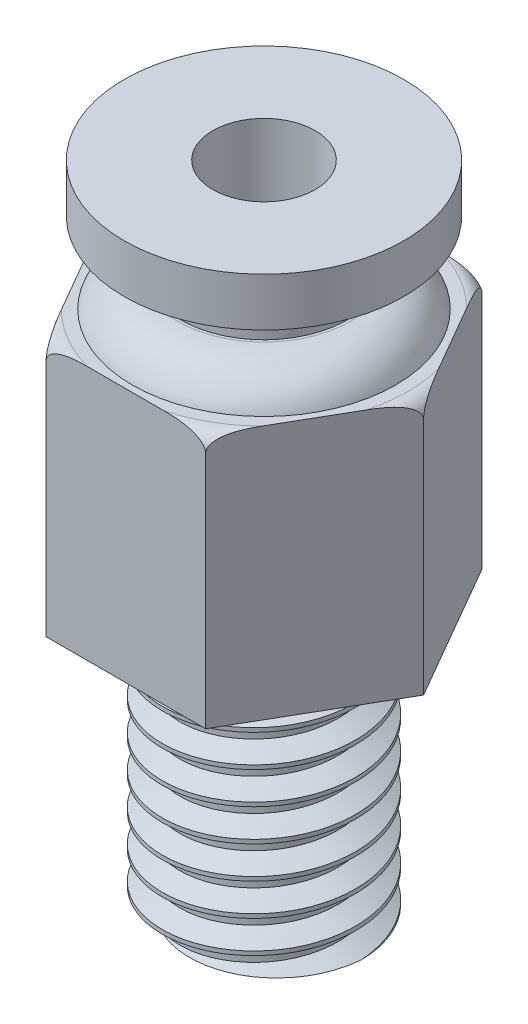
SolidWorks part; units mm, degrees
material "Acero inoxidable fundido"
ref_plane "Alzado" through (0, 0, 0) normal (0, 0, 1) x (1, 0, 0)
ref_plane "Planta" through (0, 0, 0) normal (0, 1, 0) x (1, 0, 0)
ref_plane "Vista lateral" through (0, 0, 0) normal (1, 0, 0) x (0, 0, -1)
sketch "Croquis1" plane through (0, 0, 0) normal (0, 0, 1) x (1, 0, 0)
  line L0 (-1.5875, 0) -> (-3, 0)
  line L1 (-3, 0) -> (-3, 8.1)
  line L2 (-3, 8.1) -> (-4.95, 8.1)
  line L3 (-4.95, 8.1) -> (-4.95, 16)
  line L4 (-4.95, 16) -> (-4.0875, 16)
  line L5 (-4.0875, 16) -> (-4.0875, 17)
  line L6 (-4.0875, 17) -> (-1.5875, 17)
  line L7 (-1.5875, 17) -> (-1.5875, 0)
  line L8 (-4.3375, 20) -> (-1.5875, 20)
  line L9 (-2.5875, 18.5) -> (-4.3375, 18.5)
  line L10 (-4.3375, 18.5) -> (-4.3375, 20)
  line L11 (-1.5875, 20) -> (-1.5875, 17)
  line L12 (-2.5875, 18.5) -> (-2.5875, 17)
  line L13 (0, 0) -> (0, 8.7797) construction
  dimension "D1" = 1.5875
  dimension "D2" = 3
  dimension "D3" = 4.95
  dimension "D4" = 8.1
  dimension "D5" = 20
  dimension "D6" = 1.5
  dimension "D7" = 1.5
  dimension "D8" = 1
  dimension "D9" = 2.5
  dimension "D10" = 1
  dimension "D11" = 2.75
  dimension "D12" = 7.9
revolve "Revolución1" add sketch "Croquis1" angle 360 about L13 region at (-2.9667, 10.0649, 0)
fillet "Redondeo1" radius 1.5 1 edges at (0, 17, -4.0875)
fillet "Redondeo2" radius 0.5 1 edges at (0, 16, -4.95)
thread "Rosca1" pitch 1 method cut profile "Perfil de rosca1" start angle 0, offset 1, length 10, pitch 1, diameter 6
ref_plane "Plano1" through (3, -1, 0) normal (0, 0, 1) x (1, 0, 0)
sketch "Perfil de rosca1" plane through (3, -1, 0) normal (0, 0, 1) x (1, 0, 0)
  line L0 (0, 0) -> (0, 1) construction
  line L11 (0, 0) -> (0, 0.875)
  line L12 (0, 0.875) -> (-0.5413, 0.5625)
  line L13 (-0.5413, 0.5625) -> (-0.5413, 0.3125)
  line L15 (-0.5413, 0.3125) -> (0, 0)
  line L17 (-0.5413, 0.4375) -> (0, 0.4375) construction
  point P2 (0, 0)
  dimension "Pitch" = 1
  dimension "Profile_Angle" = 60
  dimension "Profile_Land" = 0.25
  dimension "Profile_Height" = 0.5413
sketch "Croquis5" plane through (0, 0, 0) normal (0, 0, 1) x (1, 0, 0)
  line L0 (-1.5875, 20) -> (-1.5875, 17) construction
  line L1 (-4.3375, 20) -> (-1.5875, 20) construction
  line L2 (-4.3375, 18.5) -> (-4.3375, 20) construction
  line L3 (-2.5875, 18.5) -> (-4.3375, 18.5) construction
  line L4 (-2.5875, 18.5) -> (-2.5875, 17) construction
  line L5 (-4.0875, 17) -> (-1.5875, 17) construction
  line L6 (-4.0875, 16) -> (-4.0875, 17) construction
  line L7 (-4.95, 16) -> (-4.0875, 16) construction
  line L8 (-4.95, 8.1) -> (-4.95, 16) construction
  line L9 (-3, 8.1) -> (-4.95, 8.1) construction
  line L10 (-3, 0) -> (-3, 8.1) construction
  line L11 (-1.5875, 0) -> (-3, 0) construction
  line L12 (-1.5875, 17) -> (-1.5875, 0) construction
  line L13 (-1.5875, 20) -> (-1.5875, 17)
  line L14 (-4.3375, 20) -> (-1.5875, 20)
  line L15 (-4.3375, 18.5) -> (-4.3375, 20)
  line L16 (-2.5875, 18.5) -> (-4.3375, 18.5)
  line L17 (-2.5875, 18.5) -> (-2.5875, 17)
  line L18 (-4.0875, 17) -> (-1.5875, 17)
  line L19 (-4.0875, 16) -> (-4.0875, 17)
  line L20 (-4.95, 16) -> (-4.0875, 16)
  line L21 (-4.95, 8.1) -> (-4.95, 16)
  line L22 (-3, 8.1) -> (-4.95, 8.1)
  line L23 (-3, 0) -> (-3, 8.1)
  line L24 (-1.5875, 0) -> (-3, 0)
  line L25 (-1.5875, 17) -> (-1.5875, 0)
  line L26 (0, 0) -> (0, 5.0625) construction
  spline S0 degree 2 poles (-0.9409, 0) (-0.4891, 0.0325) (0, 0.0625) (1.0184, 0.125) (1.7386, 0.1875) (2.4587, 0.25) (2.4587, 0.3125) (2.4587, 0.375) (1.7386, 0.4375) (1.0184, 0.5) (0, 0.5625) (-1.0184, 0.625) (-1.7386, 0.6875) (-2.4587, 0.75) (-2.4587, 0.8125) (-2.4587, 0.875) (-1.7386, 0.9375) (-1.0184, 1) (0, 1.0625) (1.0184, 1.125) (1.7386, 1.1875) (2.4587, 1.25) (2.4587, 1.3125) (2.4587, 1.375) (1.7386, 1.4375) (1.0184, 1.5) (0, 1.5625) (-1.0184, 1.625) (-1.7386, 1.6875) (-2.4587, 1.75) (-2.4587, 1.8125) (-2.4587, 1.875) (-1.7386, 1.9375) (-1.0184, 2) (0, 2.0625) (1.0184, 2.125) (1.7386, 2.1875) (2.4587, 2.25) (2.4587, 2.3125) (2.4587, 2.375) (1.7386, 2.4375) (1.0184, 2.5) (0, 2.5625) (-1.0184, 2.625) (-1.7386, 2.6875) (-2.4587, 2.75) (-2.4587, 2.8125) (-2.4587, 2.875) (-1.7386, 2.9375) (-1.0184, 3) (0, 3.0625) (1.0184, 3.125) (1.7386, 3.1875) (2.4587, 3.25) (2.4587, 3.3125) (2.4587, 3.375) (1.7386, 3.4375) (1.0184, 3.5) (0, 3.5625) (-1.0184, 3.625) (-1.7386, 3.6875) (-2.4587, 3.75) (-2.4587, 3.8125) (-2.4587, 3.875) (-1.7386, 3.9375) (-1.0184, 4) (0, 4.0625) (1.0184, 4.125) (1.7386, 4.1875) (2.4587, 4.25) (2.4587, 4.3125) (2.4587, 4.375) (1.7386, 4.4375) (1.0184, 4.5) (0, 4.5625) (-1.0184, 4.625) (-1.7386, 4.6875) (-2.4587, 4.75) (-2.4587, 4.8125) (-2.4587, 4.875) (-1.7386, 4.9375) (-1.0184, 5) (0, 5.0625) (1.0184, 5.125) (1.7386, 5.1875) (2.4587, 5.25) (2.4587, 5.3125) (2.4587, 5.375) (1.7386, 5.4375) (1.0184, 5.5) (0, 5.5625) (-1.0184, 5.625) (-1.7386, 5.6875) (-2.4587, 5.75) (-2.4587, 5.8125) (-2.4587, 5.875) (-1.7386, 5.9375) (-1.0184, 6) (0, 6.0625) (1.0184, 6.125) (1.7386, 6.1875) (2.4587, 6.25) (2.4587, 6.3125) (2.4587, 6.375) (1.7386, 6.4375) (1.0184, 6.5) (0, 6.5625) (-1.0184, 6.625) (-1.7386, 6.6875) (-2.4587, 6.75) (-2.4587, 6.8125) (-2.4587, 6.875) (-1.7386, 6.9375) (-1.0184, 7) (0, 7.0625) (1.0184, 7.125) (1.7386, 7.1875) (2.4587, 7.25) (2.4587, 7.3125) (2.4587, 7.375) (1.7386, 7.4375) (1.0184, 7.5) (0, 7.5625) (-1.0184, 7.625) (-1.7386, 7.6875) (-2.4587, 7.75) (-2.4587, 7.8125) (-2.4587, 7.875) (-1.7386, 7.9375) (-1.0184, 8) (0, 8.0625) (1.0184, 8.125) (1.7386, 8.1875) (2.4587, 8.25) (2.4587, 8.3125) (2.4587, 8.375) (1.7386, 8.4375) (1.0184, 8.5) (0, 8.5625) (-1.0184, 8.625) (-1.7386, 8.6875) (-2.4587, 8.75) (-2.4587, 8.8125) (-2.4587, 8.875) (-1.7386, 8.9375) (-1.0184, 9) (0, 9.0625) (1.0184, 9.125) (1.7386, 9.1875) (2.4587, 9.25) (2.4587, 9.3125) knots 0.06875 0.06875 0.06875 0.075 0.075 0.0875 0.0875 0.1 0.1 0.1125 0.1125 0.125 0.125 0.1375 0.1375 0.15 0.15 0.1625 0.1625 0.175 0.175 0.1875 0.1875 0.2 0.2 0.2125 0.2125 0.225 0.225 0.2375 0.2375 0.25 0.25 0.2625 0.2625 0.275 0.275 0.2875 0.2875 0.3 0.3 0.3125 0.3125 0.325 0.325 0.3375 0.3375 0.35 0.35 0.3625 0.3625 0.375 0.375 0.3875 0.3875 0.4 0.4 0.4125 0.4125 0.425 0.425 0.4375 0.4375 0.45 0.45 0.4625 0.4625 0.475 0.475 0.4875 0.4875 0.5 0.5 0.5125 0.5125 0.525 0.525 0.5375 0.5375 0.55 0.55 0.5625 0.5625 0.575 0.575 0.5875 0.5875 0.6 0.6 0.6125 0.6125 0.625 0.625 0.6375 0.6375 0.65 0.65 0.6625 0.6625 0.675 0.675 0.6875 0.6875 0.7 0.7 0.7125 0.7125 0.725 0.725 0.7375 0.7375 0.75 0.75 0.7625 0.7625 0.775 0.775 0.7875 0.7875 0.8 0.8 0.8125 0.8125 0.825 0.825 0.8375 0.8375 0.85 0.85 0.8625 0.8625 0.875 0.875 0.8875 0.8875 0.9 0.9 0.9125 0.9125 0.925 0.925 0.9375 0.9375 0.95 0.95 0.9625 0.9625 0.975 0.975 0.9875 0.9875 1 1 1 weights 0.96194 0.96194 1 0.92388 1 0.92388 1 0.92388 1 0.92388 1 0.92388 1 0.92388 1 0.92388 1 0.92388 1 0.92388 1 0.92388 1 0.92388 1 0.92388 1 0.92388 1 0.92388 1 0.92388 1 0.92388 1 0.92388 1 0.92388 1 0.92388 1 0.92388 1 0.92388 1 0.92388 1 0.92388 1 0.92388 1 0.92388 1 0.92388 1 0.92388 1 0.92388 1 0.92388 1 0.92388 1 0.92388 1 0.92388 1 0.92388 1 0.92388 1 0.92388 1 0.92388 1 0.92388 1 0.92388 1 0.92388 1 0.92388 1 0.92388 1 0.92388 1 0.92388 1 0.92388 1 0.92388 1 0.92388 1 0.92388 1 0.92388 1 0.92388 1 0.92388 1 0.92388 1 0.92388 1 0.92388 1 0.92388 1 0.92388 1 0.92388 1 0.92388 1 0.92388 1 0.92388 1 0.92388 1 0.92388 1 0.92388 1 0.92388 1 0.92388 1 0.92388 1 0.92388 1 0.92388 1 0.92388 1 0.92388 1 0.92388 1 0.92388 1 0.92388 1 0.92388 1 0.92388 1 construction
revolve "Revolución2" add sketch "Croquis5" angle 360 about L26 region at (-2.7292, 18.85, 0)
sketch "Croquis7" plane through (0, 8.1, 0) normal (0, -1, 0) x (1, 0, 0)
  line L1 (-4.95, 0) -> (-2.475, -4.2868)
  line L2 (-2.475, -4.2868) -> (2.475, -4.2868)
  line L3 (2.475, -4.2868) -> (4.95, 0)
  line L4 (4.95, 0) -> (2.475, 4.2868)
  line L5 (2.475, 4.2868) -> (-2.475, 4.2868)
  line L6 (-2.475, 4.2868) -> (-4.95, 0)
  circle A0 centre (0, 0) radius 4.2868 construction
extrude "Cortar-Extruir-Lámina3" cut sketch "Croquis7" against normal blind 10 thin thin type one direction wall 10
